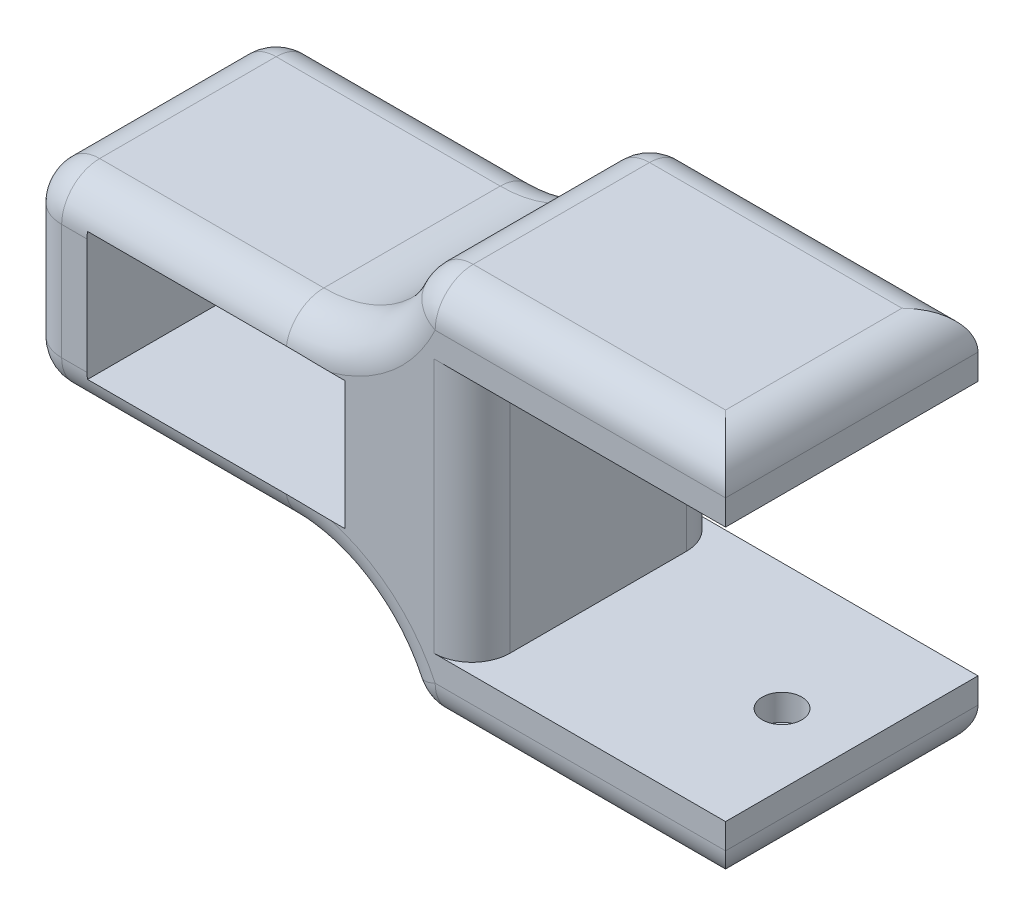
SolidWorks part; units mm, degrees
ref_plane "Front Plane" through (0, 0, 0) normal (0, 0, 1) x (1, 0, 0)
ref_plane "Top Plane" through (0, 0, 0) normal (0, 1, 0) x (1, 0, 0)
ref_plane "Right Plane" through (0, 0, 0) normal (1, 0, 0) x (0, 0, -1)
sketch "Sketch1" plane through (0, 0, 0) normal (0, 0, 1) x (1, 0, 0)
  line L1 (-30, 12.5) -> (30, 12.5)
  line L2 (-30, 12.5) -> (-30, -12.5)
  line L3 (-30, -12.5) -> (30, -12.5)
  line L4 (30, 12.5) -> (30, -12.5)
  line L5 (-30, 12.5) -> (30, -12.5) construction
  line L6 (-30, -12.5) -> (30, 12.5) construction
  point P0 (0, 0)
  dimension "D1" = 60
  dimension "D2" = 25
extrude "Boss-Extrude1" add sketch "Sketch1" along normal blind 50
sketch "Sketch5" plane through (0, 12.5, 0) normal (0, 1, 0) x (1, 0, 0)
  line L4 (30, 0) -> (-30, 0)
  line L5 (-30, 0) -> (-30, -50)
  line L6 (-30, -50) -> (30, -50)
  line L7 (30, -50) -> (30, 0)
  line L8 (30, 0) -> (-30, 0)
  line L9 (-30, 0) -> (-30, -50)
  line L10 (-30, -50) -> (30, -50)
  line L11 (30, -50) -> (30, 0)
  dimension "D1" = 0
extrude "Boss-Extrude2" add sketch "Sketch5" along normal blind 4.8
sketch "Sketch7" plane through (0, -12.5, 0) normal (0, -1, 0) x (1, 0, 0)
  line L4 (-30, 0) -> (30, 0)
  line L5 (30, 0) -> (30, 50)
  line L6 (30, 50) -> (-30, 50)
  line L7 (-30, 50) -> (-30, 0)
  line L8 (-30, 0) -> (30, 0)
  line L9 (30, 0) -> (30, 50)
  line L10 (30, 50) -> (-30, 50)
  line L11 (-30, 50) -> (-30, 0)
  dimension "D1" = 0
extrude "Boss-Extrude3" add sketch "Sketch7" along normal blind 2.61
sketch "Sketch8" plane through (0, 17.3, 0) normal (0, 1, 0) x (1, 0, 0)
  line L4 (30, -50) -> (30, 0)
  line L5 (30, 0) -> (-30, 0)
  line L6 (-30, 0) -> (-30, -50)
  line L7 (-30, -50) -> (30, -50)
  line L8 (30, -50) -> (30, 0)
  line L9 (30, 0) -> (-30, 0)
  line L10 (-30, 0) -> (-30, -50)
  line L11 (-30, -50) -> (30, -50)
  dimension "D1" = 0
extrude "Boss-Extrude4" add sketch "Sketch8" along normal blind 2.81
sketch "Sketch11" plane through (0, 0, 0) normal (0, 0, -1) x (-1, 0, 0)
  line L4 (30, -15.11) -> (30, 20.11)
  line L5 (30, 20.11) -> (-30, 20.11)
  line L6 (-30, 20.11) -> (-30, -15.11)
  line L7 (-30, -15.11) -> (30, -15.11)
  line L9 (30, 20.11) -> (-30, 20.11)
  line L10 (-30, 20.11) -> (-30, -15.11)
  line L11 (-30, -15.11) -> (30, -15.11)
  line L12 (30, -15.11) -> (30, 20.11)
  dimension "D1" = 0
extrude "Cut-Extrude4" cut sketch "Sketch11" against normal blind 10.18
sketch "Sketch2" plane through (0, 0, 50) normal (0, 0, 1) x (1, 0, 0)
  line L5 (-20.36, 10.11) -> (20.36, 10.11)
  line L6 (-20.36, 10.11) -> (-20.36, -10.11)
  line L7 (-20.36, -10.11) -> (20.36, -10.11)
  line L8 (20.36, 10.11) -> (20.36, -10.11)
  line L9 (-20.36, 10.11) -> (20.36, -10.11) construction
  line L10 (-20.36, -10.11) -> (20.36, 10.11) construction
  point P0 (0, 0)
  dimension "D1" = 40.72
  dimension "D2" = 20.22
extrude "Cut-Extrude1" cut sketch "Sketch2" against normal blind 28.82
sketch "Sketch9" plane through (-30, 0, 0) normal (-1, 0, 0) x (0, 0, 1)
  line L4 (10.18, 20.11) -> (10.18, -15.11)
  line L5 (10.18, -15.11) -> (50, -15.11)
  line L6 (50, -15.11) -> (50, 20.11)
  line L7 (50, 20.11) -> (10.18, 20.11)
  line L9 (10.18, -15.11) -> (50, -15.11)
  line L10 (50, -15.11) -> (50, 20.11)
  line L11 (50, 20.11) -> (10.18, 20.11)
  line L12 (10.18, 20.11) -> (10.18, -15.11)
  dimension "D1" = 0
extrude "Cut-Extrude3" cut sketch "Sketch9" against normal blind 4.64
sketch "Sketch16" plane through (30, 0, 0) normal (1, 0, 0) x (0, 0, -1)
  line L4 (-10.18, 20.11) -> (-50, 20.11)
  line L5 (-50, 20.11) -> (-50, -15.11)
  line L6 (-50, -15.11) -> (-10.18, -15.11)
  line L7 (-10.18, -15.11) -> (-10.18, 20.11)
  line L9 (-50, 20.11) -> (-50, -15.11)
  line L10 (-50, -15.11) -> (-10.18, -15.11)
  line L11 (-10.18, -15.11) -> (-10.18, 20.11)
  line L12 (-10.18, 20.11) -> (-50, 20.11)
  dimension "D1" = 0
extrude "Boss-Extrude8" add sketch "Sketch16" along normal blind 0.36
sketch "Sketch17" plane through (-25.36, 0, 0) normal (-1, 0, 0) x (0, 0, 1)
  line L4 (10.18, 20.11) -> (10.18, -15.11)
  line L5 (10.18, -15.11) -> (50, -15.11)
  line L6 (50, -15.11) -> (50, 20.11)
  line L7 (50, 20.11) -> (10.18, 20.11)
  line L8 (10.18, 20.11) -> (10.18, -15.11)
  line L9 (10.18, -15.11) -> (50, -15.11)
  line L10 (50, -15.11) -> (50, 20.11)
  line L11 (50, 20.11) -> (10.18, 20.11)
  dimension "D1" = 0
extrude "Boss-Extrude9" add sketch "Sketch17" along normal blind 5
sketch "Sketch20" plane through (-20.36, 0, 0) normal (1, 0, 0) x (0, 0, -1)
  line L4 (-21.18, 4.4) -> (-21.18, -4.4)
  line L5 (-29.42, -4.4) -> (-21.18, -4.4)
  line L6 (-29.42, 4.4) -> (-29.42, -4.4)
  line L7 (-29.42, 4.4) -> (-21.18, 4.4)
extrude "Cut-Extrude7" cut sketch "Sketch20" against normal blind 30
sketch "Sketch24" plane through (0, 0, 21.18) normal (0, 0, 1) x (1, 0, 0)
  line L0 (-20.36, -7.255) -> (20.36, -7.255)
  line L1 (-20.36, -4.4) -> (-20.36, -10.11) construction
  line L2 (20.36, -10.11) -> (20.36, 10.11) construction
  line L3 (-20.36, 7.255) -> (20.36, 7.255)
  line L4 (-20.36, 10.11) -> (-20.36, 4.4) construction
  line L5 (20.36, 7.255) -> (20.36, -7.255)
  line L6 (-20.36, -7.255) -> (-20.36, -4.4)
  line L7 (-20.36, -4.4) -> (-30.36, -4.4)
  line L8 (-30.36, -4.4) -> (-30.36, 4.4)
  line L9 (-30.36, 4.4) -> (-20.36, 4.4)
  line L10 (-20.36, 4.4) -> (-20.36, 7.255)
extrude "Cut-Extrude10" cut sketch "Sketch24" against normal blind 7
sketch "Sketch26" plane through (0, 20.11, 0) normal (0, 1, 0) x (1, 0, 0)
  line L4 (30.36, -10.18) -> (-30.36, -10.18)
  line L5 (-30.36, -10.18) -> (-30.36, -50)
  line L6 (-30.36, -50) -> (30.36, -50)
  line L7 (30.36, -50) -> (30.36, -10.18)
  line L8 (30.36, -10.18) -> (-30.36, -10.18)
  line L9 (-30.36, -10.18) -> (-30.36, -50)
  line L10 (-30.36, -50) -> (30.36, -50)
  line L11 (30.36, -50) -> (30.36, -10.18)
  dimension "D1" = 0
extrude "Cut-Extrude11" cut sketch "Sketch26" against normal blind 5
sketch "Sketch27" plane through (0, 0, 50) normal (0, 0, 1) x (1, 0, 0)
  line L0 (30.36, 15.11) -> (30.36, 30.11)
  line L1 (30.36, 30.11) -> (80.36, 30.11)
  line L2 (80.36, 30.11) -> (80.36, 20.11)
  line L3 (80.36, 20.11) -> (40.36, 20.11)
  line L4 (30.36, -15.11) -> (30.36, -30.11)
  line L5 (30.36, -30.11) -> (80.36, -30.11)
  line L6 (80.36, -30.11) -> (80.36, -20.11)
  line L7 (80.36, -20.11) -> (40.36, -20.11)
  line L8 (40.36, -20.11) -> (40.36, 20.11)
  line L9 (30.36, 15.11) -> (30.36, -15.11)
extrude "Boss-Extrude10" add sketch "Sketch27" against normal up to surface (39.82 mm away) up to face at (0, 0, 10.18)
sketch "Sketch28" plane through (20.36, 0, 0) normal (-1, 0, 0) x (0, 0, 1)
  line L0 (14.18, 7.255) -> (21.18, 7.255)
  line L1 (21.18, 7.255) -> (21.18, -7.255)
  line L2 (21.18, -7.255) -> (14.18, -7.255)
  line L3 (14.18, -7.255) -> (14.18, 7.255)
extrude "Cut-Extrude13" cut sketch "Sketch28" against normal blind 74
fillet "Fillet1" radius 20 2 edges at (30.36, 15.11, 30.09) (30.36, -15.11, 30.09)
fillet "Fillet2" radius 6 2 edges at (40.36, 0, 10.18) (40.36, 0, 50)
fillet "Fillet3" radius 6 17 edges at (23.2425, 19.2986, 10.18) (23.2425, 19.2986, 50) (23.2425, -19.2986, 50) (23.2425, -19.2986, 10.18) (-30.36, 0, 10.18) (-9.6825, 15.11, 10.18) (-9.6825, 15.11, 50) (-9.6825, -15.11, 50) (-9.6825, -15.11, 10.18) (55.36, -30.11, 10.18) (55.36, -30.11, 50) (80.36, 30.11, 30.09) (30.36, 30.11, 30.09) (30.36, -30.11, 30.09) (80.36, -30.11, 30.09) (55.36, 30.11, 10.18) (55.36, 30.11, 50)
sketch "Sketch29" plane through (0, -20.11, 0) normal (0, 1, 0) x (1, 0, 0)
  circle A0 centre (69.36, -30.09) radius 3.12
  dimension "D1" = 6.24
extrude "Cut-Extrude14" cut sketch "Sketch29" against normal blind 4.1
sketch "Sketch30" plane through (0, 20.11, 0) normal (0, -1, 0) x (1, 0, 0)
  circle A0 centre (69.36, 30.09) radius 3.12 construction
  circle A1 centre (69.36, 30.09) radius 3.12
extrude "Cut-Extrude15" cut sketch "Sketch30" against normal blind 4.1
fillet "Fillet4" radius 6 7 edges at (-28.6026, 13.3526, 11.9374) (-28.6026, -13.3526, 11.9374) (-30.36, -15.11, 30.09) (-30.36, -13.3526, 48.2426) (-30.36, 0, 50) (-30.36, 13.3526, 48.2426) (-30.36, 15.11, 30.09)
